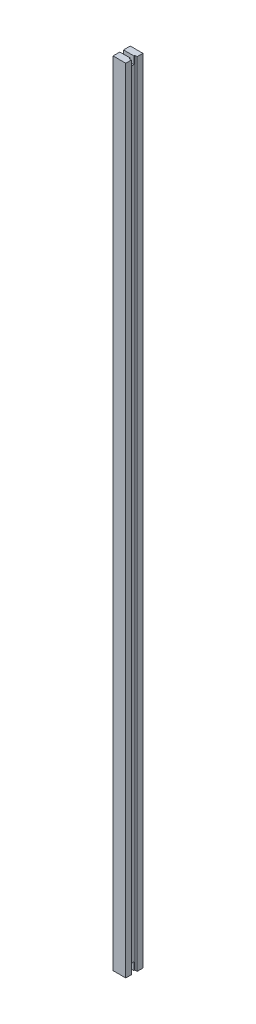
SolidWorks part; units mm, degrees
ref_plane "Спереди" through (0, 0, 0) normal (0, 0, 1) x (1, 0, 0)
ref_plane "Сверху" through (0, 0, 0) normal (0, 1, 0) x (1, 0, 0)
ref_plane "Справа" through (0, 0, 0) normal (1, 0, 0) x (0, 0, -1)
sketch "Эскиз1" plane through (0, 0, 0) normal (0, 1, 0) x (1, 0, 0)
  line L0 (-11.7649, 15) -> (10.3619, 15)
  line L1 (10.3619, 15) -> (10.3619, 5)
  line L2 (10.3619, 5) -> (6.3064, 5)
  line L3 (6.3064, 5) -> (6.3064, -5)
  line L4 (-17.598, 0) -> (16.9433, 0) construction
  line L5 (-11.7649, 15) -> (-11.7649, -15)
  line L6 (10.3619, -5) -> (6.3064, -5)
  line L7 (10.3619, -15) -> (10.3619, -5)
  line L8 (-11.7649, -15) -> (10.3619, -15)
  point P10 (-11.7649, 0)
  point P11 (6.3064, 0)
extrude "Бобышка-Вытянуть1" add sketch "Эскиз1" along normal blind 1383.55
sketch "Эскиз2" plane through (-11.7649, 0, 0) normal (-1, 0, 0) x (0, 0, 1)
  line L0 (-3.1988, 0) -> (-3.1988, 13.2878)
  line L1 (-15, 0) -> (15, 0) construction
  line L2 (-3.1988, 13.2878) -> (3.1988, 13.2878)
  line L3 (-3.1988, 0) -> (3.1988, 0)
  line L4 (0, -13.6484) -> (0, 1403.8593) construction
  line L5 (3.1988, 0) -> (3.1988, 13.2878)
  line L6 (-108.4916, 691.775) -> (106.3349, 691.775) construction
  line L7 (3.1988, 1383.55) -> (3.1988, 1370.2622)
  line L8 (-3.1988, 1383.55) -> (3.1988, 1383.55)
  line L9 (-3.1988, 1370.2622) -> (3.1988, 1370.2622)
  line L10 (-3.1988, 1383.55) -> (-3.1988, 1370.2622)
  line L11 (15, 1383.55) -> (15, 0) construction
  point P10 (0, 0)
  point P11 (0, 13.2878)
  point P19 (15, 691.775)
  point P20 (0, 1403.8593)
extrude "Вырез-Вытянуть1" cut sketch "Эскиз2" against normal through all
